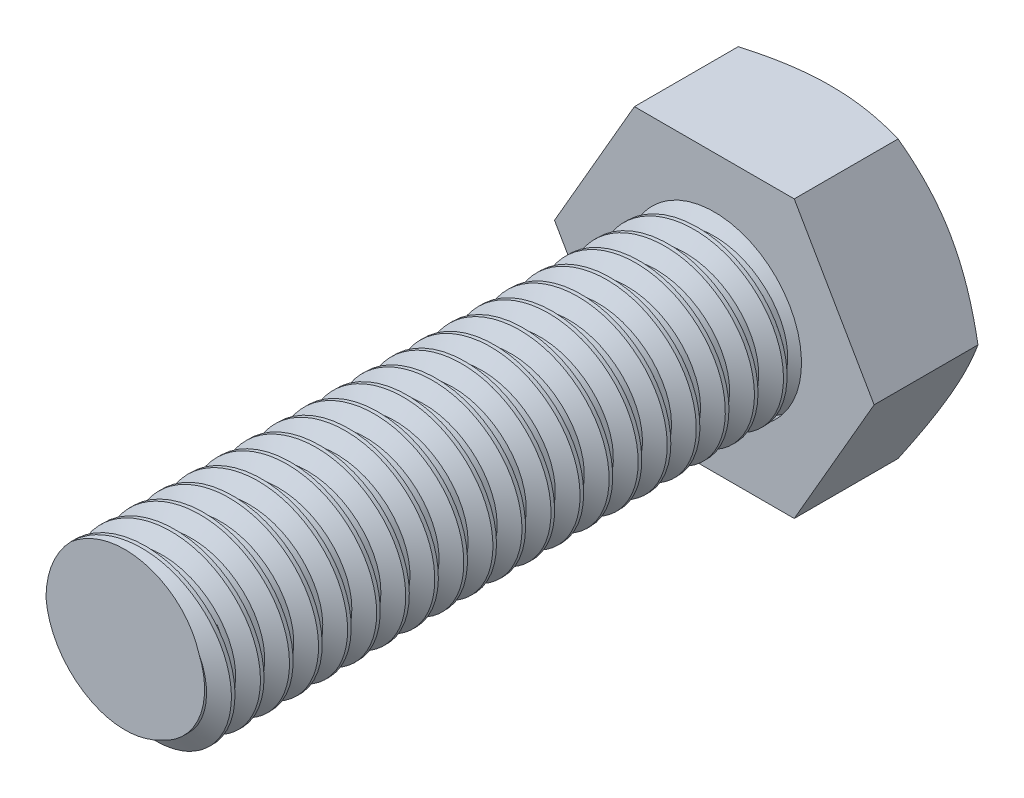
SolidWorks part; units mm, degrees
material "Alloy Steel"
ref_plane "Front Plane" through (0, 0, 0) normal (0, 0, 1) x (1, 0, 0)
ref_plane "Top Plane" through (0, 0, 0) normal (0, 1, 0) x (1, 0, 0)
ref_plane "Right Plane" through (0, 0, 0) normal (1, 0, 0) x (0, 0, -1)
sketch "Sketch1" plane through (0, 0, 0) normal (0, 0, 1) x (1, 0, 0)
  line L1 (1.375, 2.3816) -> (-1.375, 2.3816)
  line L2 (-1.375, 2.3816) -> (-2.75, 0)
  line L3 (-2.75, 0) -> (-1.375, -2.3816)
  line L4 (-1.375, -2.3816) -> (1.375, -2.3816)
  line L5 (1.375, -2.3816) -> (2.75, 0)
  line L6 (2.75, 0) -> (1.375, 2.3816)
  circle A0 centre (0, 0) radius 2.3816 construction
  dimension "D1" = 5.5
extrude "Boss-Extrude1" add sketch "Sketch1" along normal blind 1 and the other way blind 1 contours L1 L2 L3 L4 L5 L6
sketch "Sketch2" plane through (0, 0, 1) normal (0, 0, 1) x (1, 0, 0)
  circle A0 centre (0, 0) radius 1.5
extrude "Boss-Extrude2" add sketch "Sketch2" along normal blind 10
thread "Thread1" pitch 0.5 method cut profile "Thread Profile1" start angle 0, offset 1, length 0, pitch 0.5, diameter 3
ref_plane "Plane1" through (-1.5, 0, 12) normal (0, -1, 0) x (-1, 0, 0)
sketch "Thread Profile1" plane through (-1.5, 0, 12) normal (0, -1, 0) x (-1, 0, 0)
  line L0 (0, 0) -> (0, 0.5) construction
  line L11 (0, 0) -> (0, 0.4375)
  line L12 (0, 0.4375) -> (-0.2706, 0.2812)
  line L13 (-0.2706, 0.2812) -> (-0.2706, 0.1562)
  line L15 (-0.2706, 0.1562) -> (0, 0)
  line L17 (-0.2706, 0.2187) -> (0, 0.2187) construction
  point P2 (0, 0)
  dimension "Pitch" = 0.5
  dimension "Profile_Angle" = 60
  dimension "Profile_Land" = 0.125
  dimension "Profile_Height" = 0.2706
sketch "Sketch24" plane through (0, 0, -1) normal (0, 0, -1) x (-1, 0, 0)
  line L0 (1.375, -2.3816) -> (-1.375, -2.3816) construction
  circle A0 centre (0, 0) radius 2.3816
extrude "Cut-Extrude3" cut sketch "Sketch24" against normal blind 0.75 draft 60 flip side to cut contours A0
ref_axis "Axis1" through (0, 0, 15.1557) along (0, 0, -1)
